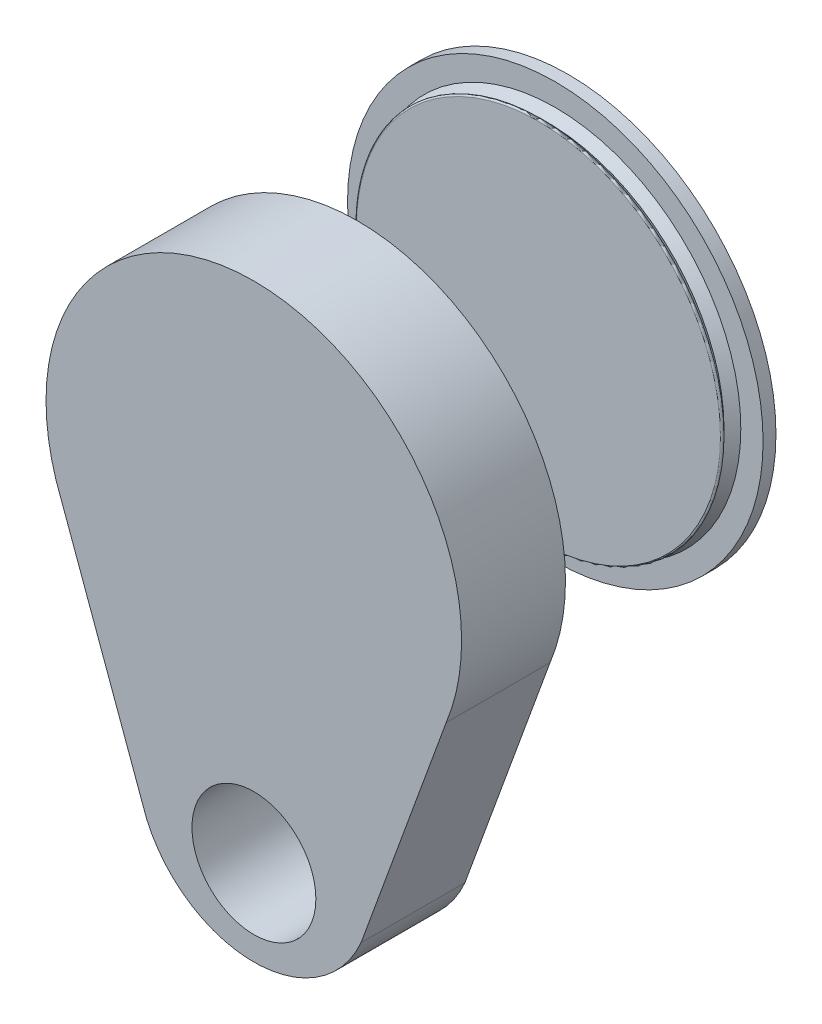
SolidWorks part; units mm, degrees
ref_plane "Plan de face" through (0, 0, 0) normal (0, 0, 1) x (1, 0, 0)
ref_plane "Plan de dessus" through (0, 0, 0) normal (0, 1, 0) x (1, 0, 0)
ref_plane "Plan de droite" through (0, 0, 0) normal (1, 0, 0) x (0, 0, -1)
sketch "Esquisse1" plane through (1.309, 0, 0) normal (0, 1, 0) x (1, 0, 0)
  line L0 (0.2535, -3.046) -> (-13.7465, -3.046)
  line L1 (-13.7465, -3.046) -> (-13.7465, 3.954)
  line L2 (-13.7465, 3.954) -> (-12.7465, 3.954)
  line L4 (-12.7465, 3.954) -> (-12.122, 3.454)
  line L5 (-12.122, 3.454) -> (-12.7465, 2.954)
  line L6 (-12.7465, 2.954) -> (-12.7465, -2.046)
  line L7 (-12.7465, -2.046) -> (0.2535, -2.046)
  line L8 (0.2535, -2.046) -> (0.2535, -3.046)
  dimension "D1" = 14
  dimension "D2" = 1
  dimension "D3" = 1
  dimension "D4" = 7
  dimension "D5" = 5
  dimension "D6" = 0.8
  dimension "D7" = 0.8
  dimension "D8" = 1
revolve "Révolution1" add sketch "Esquisse1" angle 360 about L8
sketch "Esquisse2" plane through (0, 0, -11.8007) normal (0, 1, 0) x (1, 0, 0)
  line L0 (0.0979, 5.7998) -> (-12.4021, 5.7998)
  line L1 (-12.4021, 5.7998) -> (-11.8364, 6.3655)
  line L2 (-11.8364, 6.3655) -> (-12.4021, 6.9312)
  line L3 (-12.4021, 6.9312) -> (-13.9021, 6.9312)
  line L4 (-13.9021, 6.9312) -> (-13.9021, 7.7998)
  line L5 (-13.9021, 7.7998) -> (0.0979, 7.7998)
  line L6 (0.0979, 7.7998) -> (0.0979, 5.7998)
  dimension "D1" = 2
  dimension "D2" = 12.5
  dimension "D3" = 0.8
  dimension "D4" = 0.8
  dimension "D5" = 14
revolve "Révolution2" add sketch "Esquisse2" angle 360 about L6
ref_plane "Plan1" through (0, 0, 3.046) normal (0, 0, 1) x (1, 0, 0)
ref_plane "Plan2" through (0, 0, 2.046) normal (0, 0, 1) x (1, 0, 0)
sketch "Esquisse10" plane through (0, 0, 3.046) normal (0, 0, 1) x (1, 0, 0)
  line L0 (14.8888, -4.2906) -> (8.7888, -21)
  line L1 (-5.6638, -21) -> (-11.7638, -4.2906)
  line L2 (1.5625, 0) -> (-12.4375, 0) construction
  arc A0 (14.8888, -4.2906) -> (-11.7638, -4.2906) centre (1.5625, 1.1242) cw
  circle A1 centre (1.5625, 0) radius 14 construction
  arc A2 (8.7888, -21) -> (-5.6638, -21) centre (1.5625, -17.8753) cw
  point P10 (0, 0)
  point P11 (0, 0)
  dimension "D1" = 21
  dimension "D2" = 21
extrude "Boss.-Extru.4" add sketch "Esquisse10" against normal blind 7
sketch "Esquisse11" plane through (0, 0, 3.046) normal (0, 0, 1) x (1, 0, 0)
  circle A0 centre (1.5688, -19.9708) radius 4.1753
  arc A1 (-5.6638, -21) -> (8.7888, -21) centre (1.5625, -17.8753) ccw construction
  point P2 (1.5625, -25.7482)
  dimension "D1" = 5.7775
  dimension "D2" = 7.22
  dimension "D3" = 7.2326
extrude "Enlèv. mat.-Extru.2" cut sketch "Esquisse11" against normal blind 7
fillet "Congé5" radius 0.1 1 edges at (-12.4021, 0, -17.6005)
equation "\"4.5.00mm\"=4"
